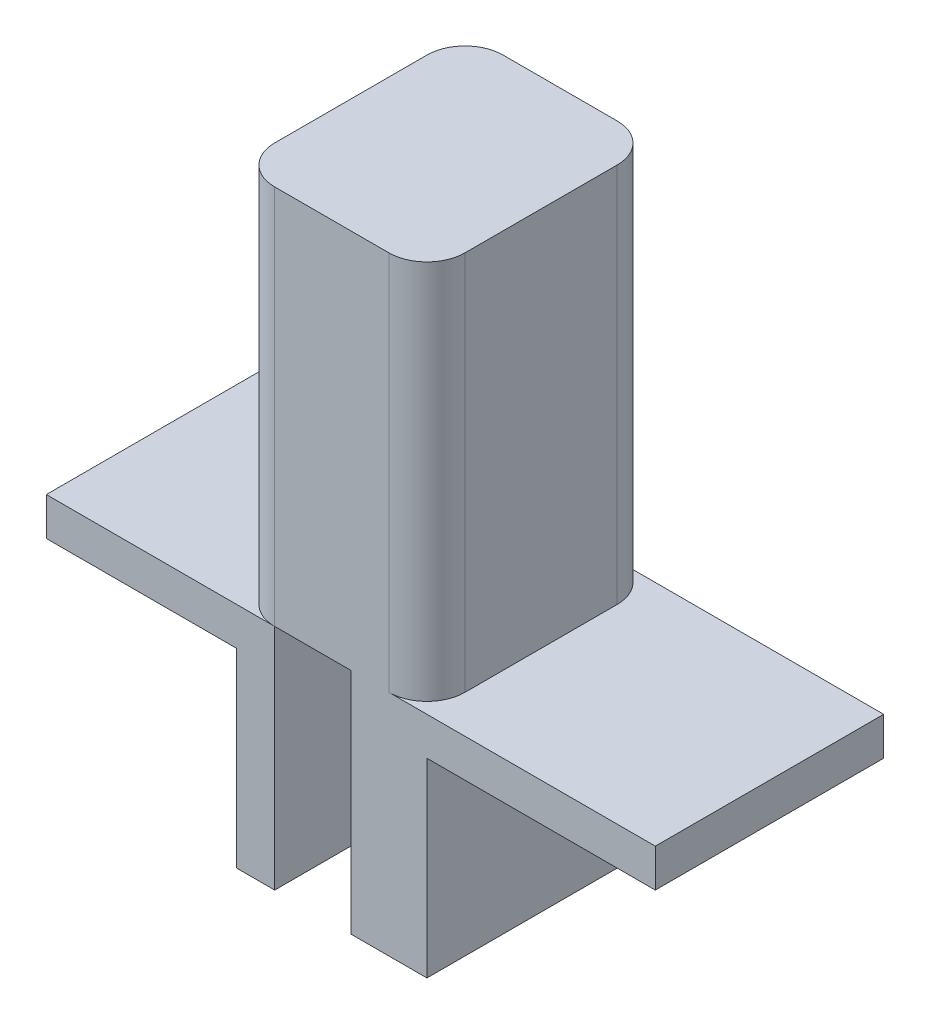
SolidWorks part; units mm, degrees
ref_plane "Front Plane" through (0, 0, 0) normal (0, 0, 1) x (1, 0, 0)
ref_plane "Top Plane" through (0, 0, 0) normal (0, 1, 0) x (1, 0, 0)
ref_plane "Right Plane" through (0, 0, 0) normal (1, 0, 0) x (0, 0, -1)
sketch "Sketch1" plane through (0, 0, 0) normal (0, 1, 0) x (1, 0, 0)
  line L1 (-1.25, 1.5) -> (1.25, 1.5)
  line L2 (-1.25, 1.5) -> (-1.25, -1.5)
  line L3 (-1.25, -1.5) -> (1.25, -1.5)
  line L4 (1.25, 1.5) -> (1.25, -1.5)
  line L5 (-1.25, 1.5) -> (1.25, -1.5) construction
  line L6 (-1.25, -1.5) -> (1.25, 1.5) construction
  point P0 (0, 0)
  dimension "D1" = 3
  dimension "D2" = 2.5
extrude "Boss-Extrude1" add sketch "Sketch1" along normal blind 1
sketch "Sketch2" plane through (0, 0, 0) normal (0, -1, 0) x (1, 0, 0)
  line L0 (1.25, -1.5) -> (-1.25, -1.5) construction
  line L1 (1.25, 1.5) -> (0.25, 1.5)
  line L2 (1.25, 1.5) -> (1.25, -1.5)
  line L3 (1.25, -1.5) -> (0.25, -1.5)
  line L4 (0.25, 1.5) -> (0.25, -1.5)
  dimension "D1" = 1
extrude "Boss-Extrude2" add sketch "Sketch2" along normal blind 3
sketch "Sketch3" plane through (0, 0, 0) normal (0, -1, 0) x (1, 0, 0)
  line L0 (0.25, -1.5) -> (-1.25, -1.5) construction
  line L1 (-1.25, 1.5) -> (-0.75, 1.5)
  line L2 (-1.25, 1.5) -> (-1.25, -1.5)
  line L3 (-1.25, -1.5) -> (-0.75, -1.5)
  line L4 (-0.75, 1.5) -> (-0.75, -1.5)
  dimension "D1" = 0.5
extrude "Boss-Extrude3" add sketch "Sketch3" along normal blind 3
sketch "Sketch4" plane through (1.25, 0, 0) normal (1, 0, 0) x (0, 0, -1)
  line L0 (-1.5, 1) -> (-1.5, -3) construction
  line L1 (-1.5, 0) -> (1.5, 0)
  line L2 (-1.5, 0) -> (-1.5, -0.5)
  line L3 (-1.5, -0.5) -> (1.5, -0.5)
  line L4 (1.5, 0) -> (1.5, -0.5)
  line L5 (1.5, 1) -> (1.5, -3) construction
  dimension "D1" = 0.5
  dimension "D2" = 0
extrude "Boss-Extrude4" add sketch "Sketch4" along normal blind 3
sketch "Sketch5" plane through (-1.25, 0, 0) normal (-1, 0, 0) x (0, 0, 1)
  line L0 (-1.5, 1) -> (-1.5, -3) construction
  line L1 (-1.5, 0) -> (1.5, 0)
  line L2 (-1.5, 0) -> (-1.5, -0.5)
  line L3 (-1.5, -0.5) -> (1.5, -0.5)
  line L4 (1.5, 0) -> (1.5, -0.5)
  line L5 (1.5, 1) -> (1.5, -3) construction
  dimension "D1" = 0.5
  dimension "D2" = 0
extrude "Boss-Extrude5" add sketch "Sketch5" along normal blind 2.5
sketch "Sketch8" plane through (0, 1, 0) normal (0, 1, 0) x (1, 0, 0)
  line L1 (-1.25, 1.5) -> (1.25, 1.5)
  line L2 (-1.25, 1.5) -> (-1.25, -1.5)
  line L3 (-1.25, -1.5) -> (1.25, -1.5)
  line L4 (1.25, 1.5) -> (1.25, -1.5)
  line L5 (-1.25, 1.5) -> (1.25, -1.5) construction
  line L6 (-1.25, -1.5) -> (1.25, 1.5) construction
  point P0 (0, 0)
extrude "Boss-Extrude6" add sketch "Sketch8" along normal blind 4
fillet "Fillet1" radius 0.5 4 edges at (-1.25, 2.5, -1.5) (1.25, 2.5, -1.5) (1.25, 2.5, 1.5) (-1.25, 2.5, 1.5)
sketch "Sketch6" plane through (0, -0.5, 0) normal (0, -1, 0) x (1, 0, 0)
  line L0 (-2.9868, 0) -> (-1.4868, 0) construction
  text T0 "Left" font "Comic Sans MS" height in points 1
  dimension "D1" = 1.5
extrude "Cut-Extrude1" [suppressed] cut sketch "Sketch6" against normal blind 0.05
sketch "Sketch7" plane through (0, -0.5, 0) normal (0, -1, 0) x (1, 0, 0)
  line L0 (1.6808, 0) -> (4.0011, 0) construction
  text T0 "Right" font "Comic Sans MS" height in points 2
extrude "Cut-Extrude3" [suppressed] cut sketch "Sketch7" against normal blind 0.05
